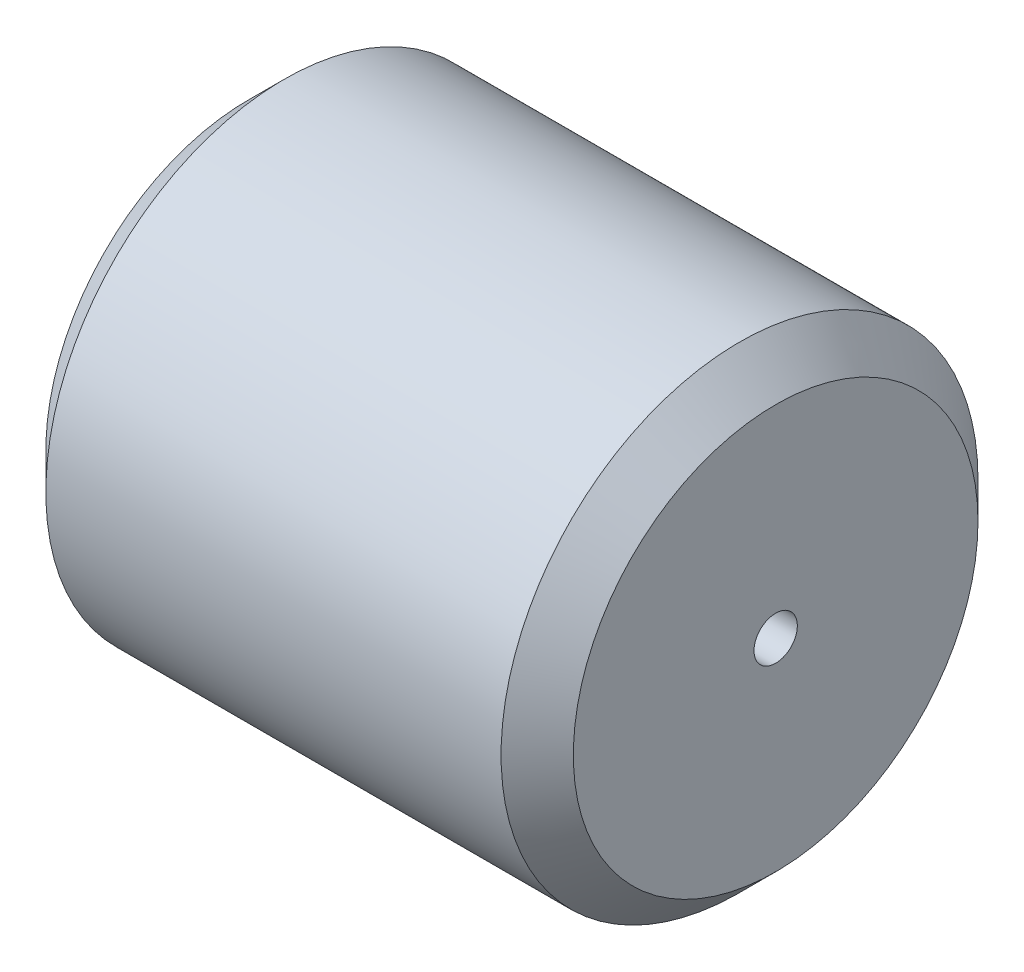
SolidWorks part; units mm, degrees
ref_plane "Front" through (0, 0, 0) normal (0, 0, 1) x (1, 0, 0)
ref_plane "Top" through (0, 0, 0) normal (0, 1, 0) x (1, 0, 0)
ref_plane "Right" through (0, 0, 0) normal (1, 0, 0) x (0, 0, -1)
ref_axis "side-side" through (80.9, 0, 0) along (-1, 0, 0)
ref_axis "up-down" through (0, 50, 0) along (0, -1, 0)
ref_axis "front-back" through (0, 0, -80.9) along (0, 0, 1)
sketch "Sketch1" plane through (0, 0, 0) normal (1, 0, 0) x (0, 0, -1)
  circle A0 centre (0, 0) radius 33
  circle A1 centre (0, 0) radius 3
  dimension "D1" = 6
  dimension "D2" = 66
extrude "Boss-Extrude1" add sketch "Sketch1" along normal mid plane 73
chamfer "Chamfer1" distance 5 angle 45 2 edges at (-36.5, 0, -33) (36.5, 0, -33)
